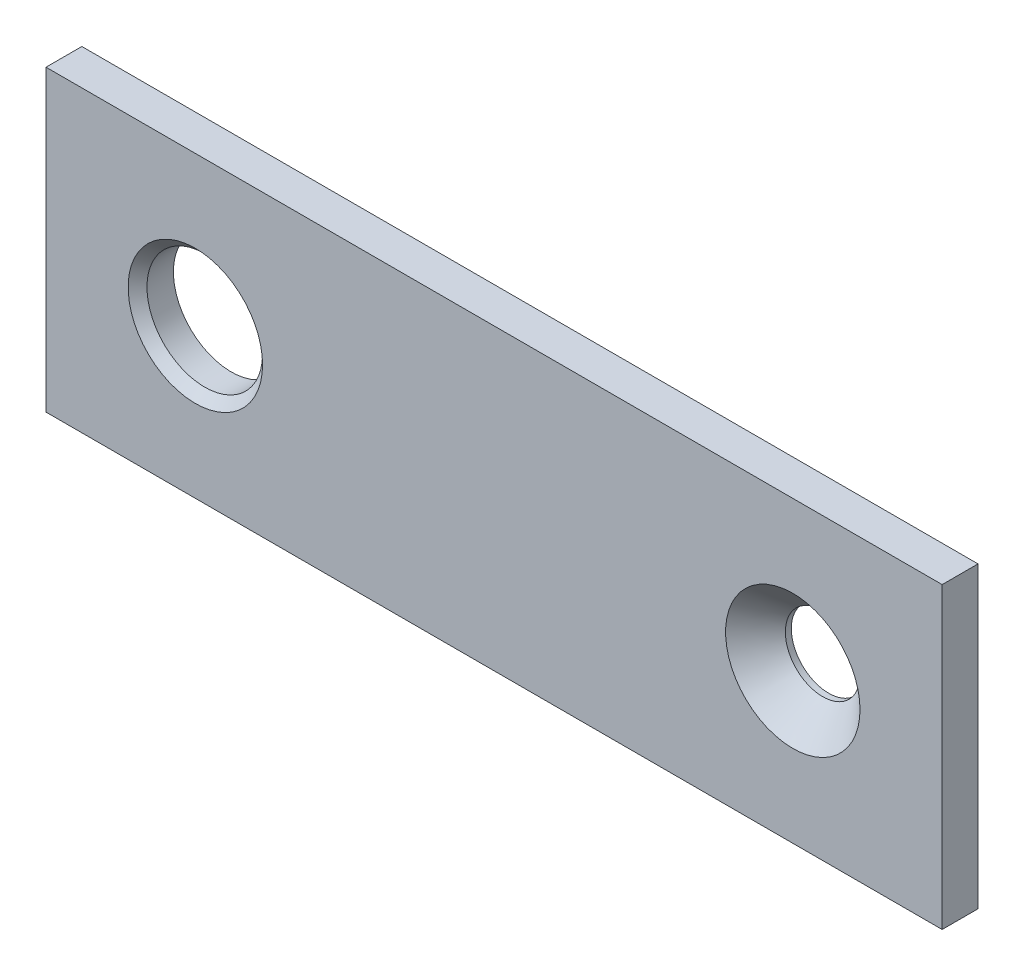
SolidWorks part; units mm, degrees
material "Plain Carbon Steel"
ref_plane "Front" through (0, 0, 0) normal (0, 0, 1) x (1, 0, 0)
ref_plane "Top" through (0, 0, 0) normal (0, 1, 0) x (1, 0, 0)
ref_plane "Right" through (0, 0, 0) normal (1, 0, 0) x (0, 0, -1)
sketch "Sketch1" plane through (0, 0, 0) normal (0, 0, 1) x (1, 0, 0)
  line L0 (-19.05, 6.35) -> (19.05, -6.35) construction
  line L1 (-19.05, 6.35) -> (19.05, 6.35)
  line L2 (-19.05, 6.35) -> (-19.05, -6.35)
  line L3 (-19.05, -6.35) -> (19.05, -6.35)
  line L4 (19.05, 6.35) -> (19.05, -6.35)
  dimension "A1" = 38.1
  dimension "B" = 12.7
extrude "Boss-Extrude1" add sketch "Sketch1" against normal blind 1.524
sketch "Sketch2" plane through (0, 0, 0) normal (0, 0, 1) x (1, 0, 0)
  line L0 (-12.7, 0) -> (-12.7, 6.35) construction
  line L1 (-12.7, 6.35) -> (-4.2333, 6.35) construction
  line L2 (4.2333, 0) -> (12.7, 0) construction
  line L3 (4.2333, 0) -> (-4.2333, 0) construction
  line L4 (-4.2333, 0) -> (-12.7, 0) construction
  line L5 (-4.2333, 6.35) -> (-4.2333, 0) construction
  line L6 (-4.2333, 6.35) -> (4.2333, 6.35) construction
  line L7 (4.2333, 6.35) -> (4.2333, 0) construction
  line L9 (4.2333, 6.35) -> (12.7, 6.35) construction
  line L10 (12.7, 6.35) -> (12.7, 0) construction
  line L11 (19.05, 6.35) -> (-19.05, 6.35) construction
  line L17 (-19.05, 6.35) -> (-19.05, -6.35) construction
  circle A0 centre (-12.7, 0) radius 1.5875
  circle A1 centre (-4.2333, 0) radius 1.5875
  circle A4 centre (4.2333, 0) radius 1.5875
  circle A5 centre (12.7, 0) radius 1.5875
extrude "Cut-Extrude1" cut sketch "Sketch2" against normal through all
chamfer "Chamfer1" distance 1.27 angle 45 4 edges at (14.2875, 0, 0) (5.8208, 0, 0) (-2.6458, 0, 0) (-11.1125, 0, 0)
other "deleteface" face at (-1.3758, 0, 0) face at (-2.6458, 0, -1.27) face at (7.0908, 0, 0) face at (5.8208, 0, -1.27) and patch yes
other "DeleteFace1" [suppressed]
sketch "Sketch3" [suppressed] plane through (0, 0, 0) normal (0, 0, 1) x (1, 0, 0)
  line L0 (-12.7, 0) -> (-7.62, 0) construction
  line L1 (-7.62, 0) -> (-2.54, 0) construction
  line L2 (-2.54, 0) -> (2.54, 0) construction
  line L3 (2.54, 0) -> (7.62, 0) construction
  line L4 (7.62, 0) -> (12.7, 0) construction
  circle A0 centre (-7.62, 0) radius 1.5875
  circle A1 centre (-2.54, 0) radius 1.5875
  circle A2 centre (2.54, 0) radius 1.5875
  circle A3 centre (7.62, 0) radius 1.5875
  circle A4 centre (-12.7, 0) radius 1.5875 construction
extrude "Cut-Extrude2" [suppressed] cut sketch "Sketch3" against normal through all
chamfer "Chamfer2" [suppressed] distance 1.27 angle 45
hole_wizard "#10 (0.1935) Diameter Hole1" positions "Sketch4" profile "Sketch5" hole size "#10" standard "ANSI Inch" end condition through all
sketch "Sketch4" plane through (0, 0, 0) normal (0, 0, 1) x (1, 0, 0)
  point P0 (-12.7, 0)
sketch "Sketch5" plane through (-12.7, 0, 0) normal (1, 0, 0) x (0, -1, 0)
  line L0 (0, 0) -> (0, 1.524)
  line L1 (0, 1.524) -> (2.4574, 1.524)
  line L2 (2.4574, 1.524) -> (2.4574, 0)
  line L5 (2.4574, 0) -> (0, 0)
  line L11 (0, -6.35) -> (0, 107.95) construction
  dimension "Thru Hole Dia." = 4.9149
  dimension "Thru Hole Depth" = 1.524
equation "\"D1@Chamfer1\" = \"Hole Size@Sketch2\" * .4"
equation "\"D1@Chamfer2\" = \"D1@Chamfer1\""
